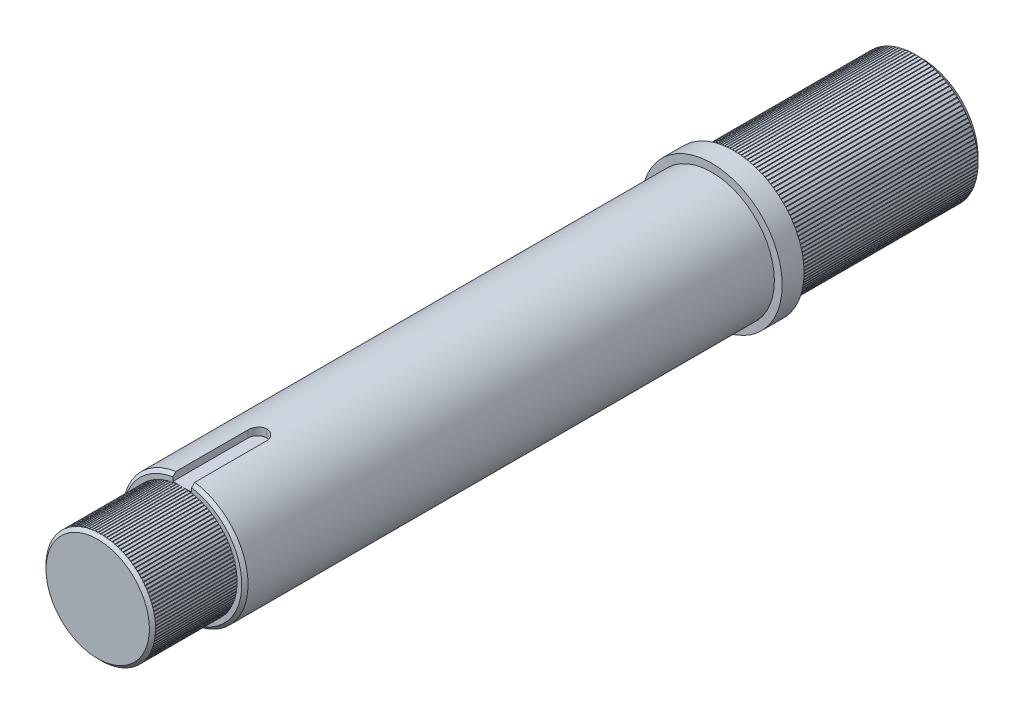
SolidWorks part; units mm, degrees
ref_plane "前视基准面" through (0, 0, 0) normal (0, 0, 1) x (1, 0, 0)
ref_plane "上视基准面" through (0, 0, 0) normal (0, 1, 0) x (1, 0, 0)
ref_plane "右视基准面" through (0, 0, 0) normal (1, 0, 0) x (0, 0, -1)
sketch "草图1" plane through (0, 0, 0) normal (1, 0, 0) x (0, 0, -1)
  line L0 (-263, 0) -> (0, 0)
  line L1 (0, 0) -> (0, 20)
  line L2 (0, 20) -> (-60, 20)
  line L3 (-60, 20) -> (-60, 22.5)
  line L4 (-60, 22.5) -> (-67, 22.5)
  line L5 (-67, 22.5) -> (-67, 20)
  line L6 (-67, 20) -> (-236, 20)
  line L7 (-236, 20) -> (-236, 17.5)
  line L8 (-236, 17.5) -> (-263, 17.5)
  line L9 (-263, 17.5) -> (-263, 0)
  dimension "D1" = 20
  dimension "D2" = 7
  dimension "D3" = 22.5
  dimension "D4" = 60
  dimension "D5" = 169
  dimension "D6" = 27
  dimension "D7" = 17.5
revolve "旋转1" add sketch "草图1" angle 360 about L0
cosmetic thread "装饰螺纹线1" parameters "D1"=32, "D2"=38
sketch "草图2" plane through (0, 0, 236) normal (0, 0, -1) x (-1, 0, 0)
  line L0 (0, 0) -> (0, 28.4467) construction
  line L1 (-3, 24.9683) -> (3, 24.9683)
  line L2 (-3, 24.9683) -> (-3, 17.5)
  line L3 (-3, 17.5) -> (3, 17.5)
  line L4 (3, 24.9683) -> (3, 17.5)
  line L5 (0, 20) -> (6.07, 20) construction
  circle A1 centre (0, 0) radius 20 construction
  dimension "D1" = 6
  dimension "D2" = 2.5
extrude "切除-拉伸1" cut sketch "草图2" along normal blind 27
fillet "圆角1" radius 3 2 edges at (3, 18.6369, 209) (-3, 18.6369, 209)
chamfer "倒角1" distance 1 angle 45 2 edges at (0, -20, 236) (17.5, 0, 263)
chamfer "倒角2" distance 2 angle 45 1 edges at (20, 0, 0)
sketch "草图3" plane through (0, 0, 263) normal (0, 0, 1) x (1, 0, 0)
  line L0 (-0.1, 17.5) -> (0, 17.4)
  line L1 (0, 17.4) -> (0.1, 17.5)
  line L2 (0.1, 17.5) -> (-0.1, 17.5)
  line L3 (0, 0) -> (0, 17.5) construction
  circle A0 centre (0, 0) radius 17.5 construction
  dimension "D1" = 0.1
extrude "切除-拉伸2" cut sketch "草图3" against normal up to surface (27 mm away) up to face at (2.9167, 8.7103, 236)
ref_axis "基准轴1" through (0, 0, 67) along (0, 0, 1)
pattern_circular "阵列(圆周)1" count 120 over 360 about axis through (0, 0, 67) along (0, 0, 1) of "切除-拉伸2"
sketch "草图4" plane through (0, 0, 0) normal (0, 0, -1) x (-1, 0, 0)
  line L0 (-0.1, 20) -> (0, 19.9)
  line L1 (0, 19.9) -> (0.1, 20)
  line L2 (0.1, 20) -> (-0.1, 20)
  line L3 (0, 0) -> (0, 20) construction
  circle A0 centre (0, 0) radius 20 construction
  dimension "D1" = 0.1
extrude "切除-拉伸3" cut sketch "草图4" against normal up to surface (60 mm away) up to face at (22.5, 0, 60)
pattern_circular "阵列(圆周)2" count 120 over 360 about axis through (0, 0, 67) along (0, 0, 1) of "切除-拉伸3"
